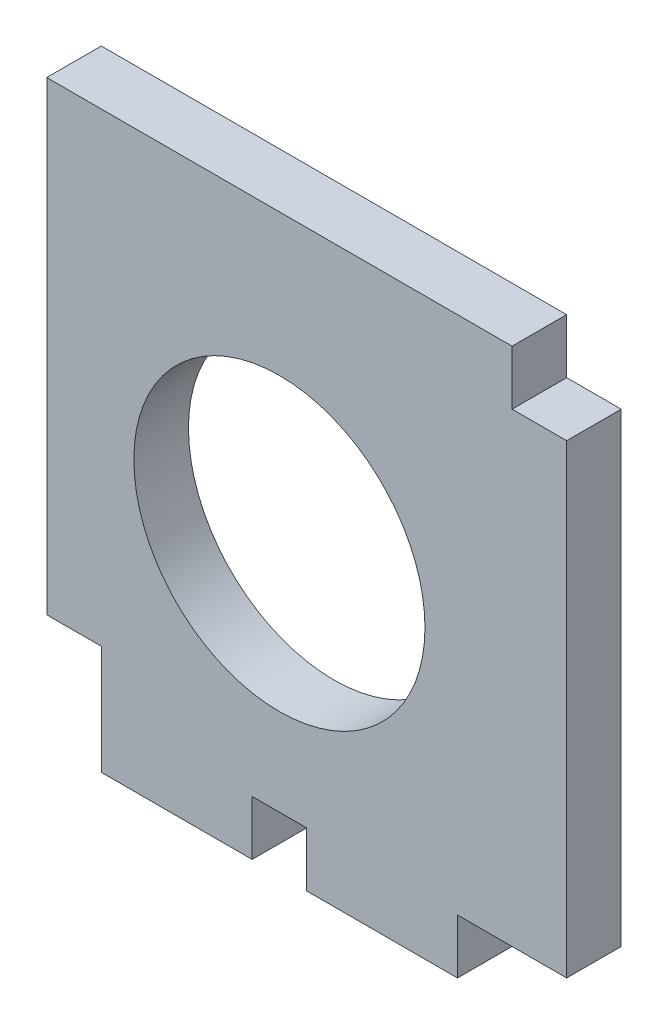
SolidWorks part; units mm, degrees
ref_plane "Front Plane" through (0, 0, 0) normal (0, 0, 1) x (1, 0, 0)
ref_plane "Top Plane" through (0, 0, 0) normal (0, 1, 0) x (1, 0, 0)
ref_plane "Right Plane" through (0, 0, 0) normal (1, 0, 0) x (0, 0, -1)
sketch "Sketch1" plane through (0, 0, 0) normal (0, 0, 1) x (1, 0, 0)
  line L0 (-20.3, -20.3) -> (-15.6929, -20.3) construction
  line L1 (-20.3, 34.9375) -> (-20.3, 54.9375) construction
  line L2 (20.3, -25.0625) -> (-20.3, -25.0625)
  line L3 (20.3, -25.0625) -> (20.3, 25.0625)
  line L4 (20.3, 25.0625) -> (-20.3, 25.0625)
  line L5 (-20.3, -25.0625) -> (-20.3, 25.0625)
  line L6 (-20.3, -20.3) -> (-15.5375, -20.3)
  line L7 (-20.3, -20.3) -> (-20.3, -15.5375)
  line L8 (20.3, -20.3) -> (20.3, 20.3) construction
  line L9 (-0.3, -25.0625) -> (19.7, -25.0625) construction
  line L10 (20.3, 20.3) -> (-20.3, 20.3) construction
  line L11 (-20.3, -20.3) -> (20.3, -20.3) construction
  line L12 (-20.3, -20.3) -> (20.3, -20.3)
  line L13 (-15.5375, -20.3) -> (-15.5375, -5.0625) construction
  line L14 (-20.3, -25.0625) -> (-15.5375, -25.0625)
  line L15 (-20.3, -25.0625) -> (-20.3, -20.3)
  line L16 (-20.3, -20.3) -> (-15.5375, -20.3)
  line L17 (-15.5375, -25.0625) -> (-15.5375, -20.3)
  line L18 (20.3, -25.0625) -> (15.5375, -25.0625)
  line L19 (20.3, -25.0625) -> (20.3, -20.3)
  line L20 (20.3, -20.3) -> (15.5375, -20.3)
  line L21 (15.5375, -25.0625) -> (15.5375, -20.3)
  line L22 (0, -25.0625) -> (0, -20.3) construction
  line L23 (25.3131, -20.3) -> (-15.6929, -20.3) construction
  line L24 (-2.3812, -20.3) -> (2.3813, -20.3)
  line L25 (-2.3812, -20.3) -> (-2.3812, -25.0625)
  line L26 (-2.3812, -25.0625) -> (2.3813, -25.0625)
  line L27 (2.3813, -20.3) -> (2.3813, -25.0625)
  line L28 (-2.3812, -20.3) -> (2.3813, -25.0625) construction
  line L29 (-2.3812, -25.0625) -> (2.3813, -20.3) construction
  line L30 (20.3, 20.3) -> (25.0625, 20.3)
  line L31 (20.3, 20.3) -> (20.3, -20.3)
  line L32 (20.3, -20.3) -> (25.0625, -20.3)
  line L33 (25.0625, 20.3) -> (25.0625, -20.3)
  line L34 (-20.3, -15.5375) -> (-15.5375, -15.5375)
  line L35 (-15.5375, -20.3) -> (-15.5375, -15.5375)
  point P23 (0, -22.6812)
  dimension "D1" = 4.7625
  dimension "D2" = 4.7625
  dimension "D3" = 4.7625
  dimension "D4" = 4.7625
  dimension "D5" = 4.7625
extrude "Boss-Extrude1" add sketch "Sketch1" along normal blind 4.7625 contours L25 L12 L17 L2 | L12 L27 L2 L21 | L5 L12 L3 L4 | L31 L30 L33 L32 region at (8.9594, -22.6812, 0) region at (0.2234, 2.6344, 0) region at (-8.9594, -22.6812, 0)
sketch "Sketch2" plane through (0, 0, 4.7625) normal (0, 0, 1) x (1, 0, 0)
  circle A0 centre (0, 0) radius 12.7
  dimension "D1" = 25.4
extrude "Cut-Extrude1" cut sketch "Sketch2" against normal through all
